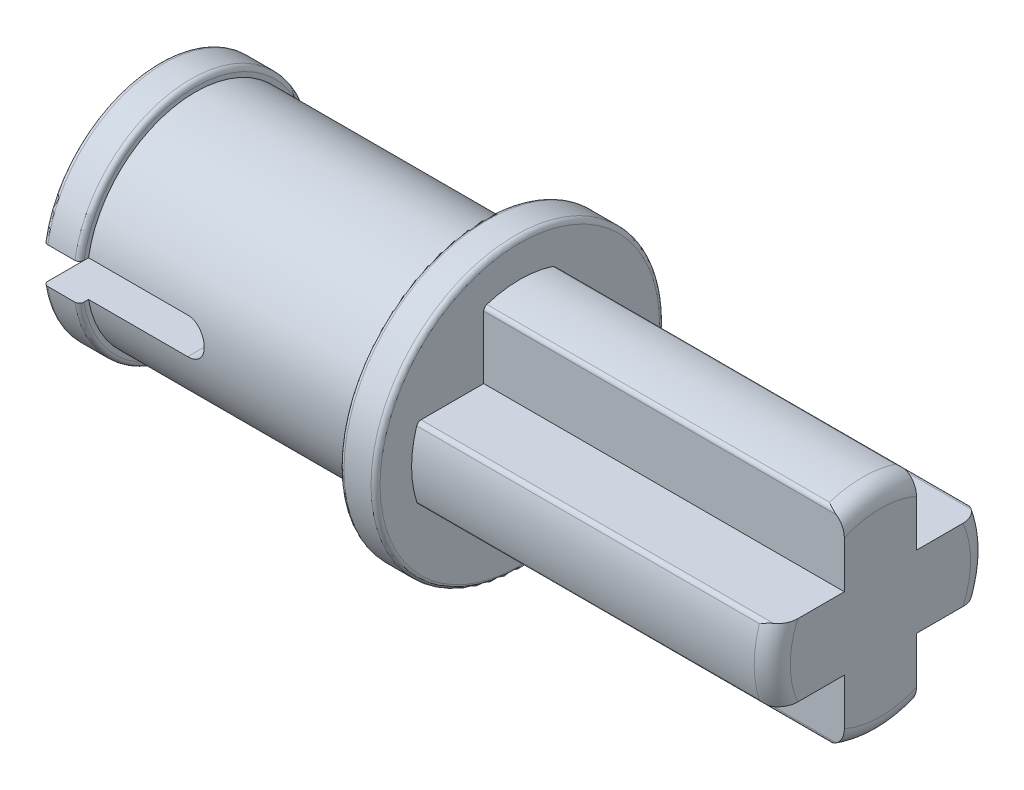
SolidWorks part; units mm, degrees
ref_plane "Front Plane" through (0, 0, 0) normal (0, 0, 1) x (1, 0, 0)
ref_plane "Top Plane" through (0, 0, 0) normal (0, 1, 0) x (1, 0, 0)
ref_plane "Right Plane" through (0, 0, 0) normal (1, 0, 0) x (0, 0, -1)
sketch "Sketch1" plane through (0, 0, 0) normal (0, 0, 1) x (1, 0, 0)
  line L0 (-5, 2.4) -> (-5, 0)
  line L1 (-5, 0) -> (-0.8, 0)
  line L2 (-0.8, 0) -> (-0.8, 2.4)
  line L3 (-0.8, 2.4) -> (-5, 2.4)
  line L4 (-5, 0) -> (-0.8, 0) construction
revolve "Revolve1" add sketch "Sketch1" angle 360 about L4
hole_wizard "Ø0.8 (0.8) Diameter Hole1" positions "3DSketch1" profile "Sketch2" hole size "Ø0.8" standard "ANSI Metric"
sketch3d "3DSketch1"
  point P0 (-5, 0, -2.4)
sketch "Sketch2" plane through (-5, 0, -2.4) normal (1, 0, 0) x (0, 1, 0)
  line L0 (0, 0) -> (0, 4.8)
  line L1 (0, 4.8) -> (0.4, 4.8)
  line L2 (0.4, 4.8) -> (0.4, 0)
  line L5 (0.4, 0) -> (0, 0)
  line L11 (0, -6.35) -> (0, 107.95) construction
  dimension "Thru Hole Dia." = 0.8
  dimension "Thru Hole Depth" = 4.8
ref_plane "Plane1" through (-0.8, 0, 0) normal (-1, 0, 0) x (0, 0, 1)
sketch "Sketch6" plane through (-0.8, 0, 0) normal (-1, 0, 0) x (0, 0, 1)
  circle A0 centre (0, 0) radius 3.2
extrude "Boss-Extrude1" add sketch "Sketch6" against normal blind 0.8
sketch "Sketch7" plane through (-5, 0, 0) normal (-1, 0, 0) x (0, 0, 1)
  line L0 (-2.569, -0.4) -> (2.569, -0.4)
  arc A0 (2.569, -0.4) -> (-2.569, -0.4) centre (0, 0) cw
extrude "Boss-Extrude2" add sketch "Sketch7" along normal blind 3
sketch "Sketch8" plane through (-5, 0, 0) normal (1, 0, 0) x (0, 0, -1)
  line L0 (2.569, -0.4) -> (2.3664, -0.4)
  line L1 (-2.3664, -0.4) -> (-2.569, -0.4)
  arc A0 (2.3664, -0.4) -> (-2.3664, -0.4) centre (0, 0) cw
  arc A1 (-2.569, -0.4) -> (2.569, -0.4) centre (0, 0) ccw
extrude "Cut-Extrude1" cut sketch "Sketch8" against normal blind 2.2
sketch "Sketch9" plane through (-5, 0, 0) normal (-1, 0, 0) x (0, 0, 1)
  line L0 (2.3664, 0.4) -> (-2.3664, 0.4)
  arc A0 (-2.3664, 0.4) -> (2.3664, 0.4) centre (0, 0) cw
extrude "Boss-Extrude3" add sketch "Sketch9" along normal blind 2.2
sketch "Sketch10" plane through (-7.2, 0, 0) normal (-1, 0, 0) x (0, 0, 1)
  line L0 (2.569, 0.4) -> (-2.569, 0.4)
  arc A0 (-2.569, 0.4) -> (2.569, 0.4) centre (0, 0) cw
extrude "Boss-Extrude4" add sketch "Sketch10" along normal blind 0.8
sketch "Sketch11" plane through (0, 0, 0) normal (1, 0, 0) x (0, 0, -1)
  line L0 (2.2627, -0.8) -> (0.8, -0.8)
  line L1 (0.8, -0.8) -> (0.8, -2.2627)
  line L2 (-0.8, -2.2627) -> (-0.8, -0.8)
  line L3 (-0.8, -0.8) -> (-2.2627, -0.8)
  line L4 (-2.2627, 0.8) -> (-0.8, 0.8)
  line L5 (-0.8, 0.8) -> (-0.8, 2.2627)
  line L6 (0.8, 2.2627) -> (0.8, 0.8)
  line L7 (0.8, 0.8) -> (2.2627, 0.8)
  arc A0 (2.2627, 0.8) -> (2.2627, -0.8) centre (0, 0) cw
  arc A1 (0.8, -2.2627) -> (-0.8, -2.2627) centre (0, 0) cw
  arc A2 (-2.2627, -0.8) -> (-2.2627, 0.8) centre (0, 0) cw
  arc A3 (-0.8, 2.2627) -> (0.8, 2.2627) centre (0, 0) cw
extrude "Boss-Extrude5" add sketch "Sketch11" along normal blind 8
ref_plane "Plane2" through (0, 0, 0) normal (0, 0, -1) x (-1, 0, 0)
sketch "Sketch16" plane through (0, 0, 0) normal (0, 0, -1) x (-1, 0, 0)
  line L0 (0.8, 1.6) -> (0.8, 0)
  line L1 (0.8, 0) -> (8, 0)
  line L2 (8, 0) -> (8, 1.6)
  line L3 (8, 1.6) -> (0.8, 1.6)
  line L4 (0.8, 0) -> (8, 0) construction
revolve "Cut-Revolve1" cut sketch "Sketch16" angle 360 about L1
fillet "Fillet1" radius 0.1 14 edges at (4, -0.8, 2.2627) (-7.2, -2.6, 0) (-8, 2.6, 0) (4, -2.2627, 0.8) (-0.8, 0, 3.2) (4, -0.8, -2.2627) (-8, -2.6, 0) (4, 2.2627, -0.8) (0, 0, 3.2) (4, 0.8, -2.2627) (-7.2, 2.6, 0) (4, -2.2627, -0.8) (4, 2.2627, 0.8) (4, 0.8, 2.2627)
fillet "Fillet2" radius 0.4 4 edges at (8, 0, 2.4) (8, -2.4, 0) (8, 2.4, 0) (8, 0, -2.4)
